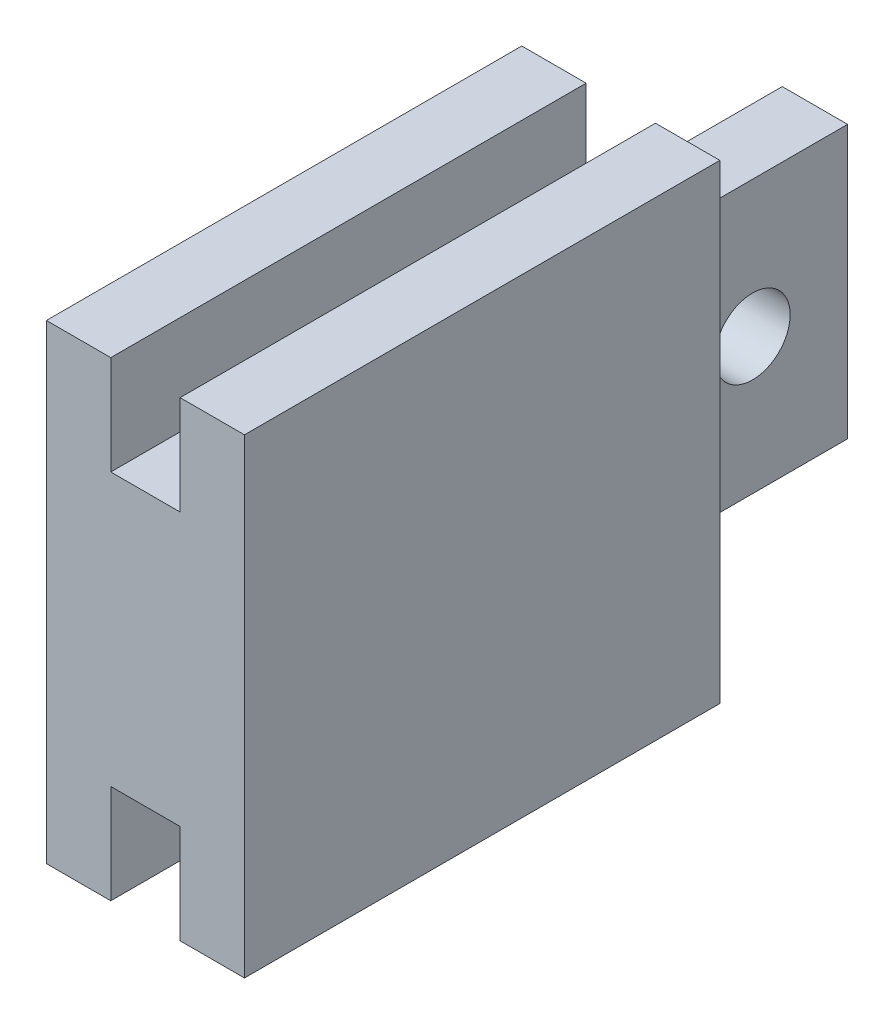
SolidWorks part; units mm, degrees
ref_plane "Front Plane" through (0, 0, 0) normal (1, 0, 0) x (0, 1, 0)
ref_plane "Top Plane" through (0, 0, 0) normal (0, 0, 1) x (0, 1, 0)
ref_plane "Right Plane" through (0, 0, 0) normal (0, 1, 0) x (-1, 0, 0)
sketch "Sketch1" plane through (0, 0, 0) normal (1, 0, 0) x (0, 1, 0)
  line L1 (0, 0) -> (23.75, 0)
  line L2 (0, 0) -> (0, 24)
  line L3 (0, 24) -> (23.75, 24)
  line L4 (23.75, 0) -> (23.75, 24)
  dimension "D1" = 23.75
  dimension "D2" = 24
extrude "Boss-Extrude1" add sketch "Sketch1" against normal blind 10
sketch "Sketch2" plane through (0, 0, 0) normal (0, -1, 0) x (1, 0, 0)
  line L1 (-10, 0) -> (-6.65, 0)
  line L2 (-10, 0) -> (-10, -9.8)
  line L3 (-10, -9.8) -> (-6.65, -9.8)
  line L4 (-6.65, 0) -> (-6.65, -9.8)
  line L5 (0, 0) -> (-3.35, 0)
  line L6 (0, 0) -> (0, -9.8)
  line L7 (0, -9.8) -> (-3.35, -9.8)
  line L8 (-3.35, 0) -> (-3.35, -9.8)
  line L9 (-6.65, -9.8) -> (-3.35, -9.8)
  line L10 (-6.65, -9.8) -> (-6.65, 0)
  line L11 (-6.65, 0) -> (-3.35, 0)
  line L12 (-3.35, -9.8) -> (-3.35, 0)
  line M12 (-10, 0) -> (0, 0)
  dimension "D1" = 9.8
  dimension "D2" = 3.35
  dimension "D3" = 3.35
extrude "Boss-Extrude2" add sketch "Sketch2" against normal through all contours L4 L9 L8 M12 region at (-5, 0, -4.9)
sketch "Sketch3" plane through (0, 0, 0) normal (0, -1, 0) x (1, 0, 0)
  line L0 (-3.35, 20.65) -> (-3.35, 3.35)
  line L1 (0, 24) -> (-10, 24)
  line L2 (0, 24) -> (0, 0)
  line L3 (0, 0) -> (-10, 0)
  line L4 (-10, 24) -> (-10, 0)
  line L5 (-3.35, 3.35) -> (-6.65, 3.35)
  line L6 (-6.65, 20.65) -> (-6.65, 3.35)
  line L7 (-3.35, 20.65) -> (-6.65, 20.65)
  line L9 (-6.65, 20.65) -> (-3.35, 20.65)
  line L10 (-6.65, 20.65) -> (-6.65, 24)
  line L11 (-6.65, 24) -> (-3.35, 24)
  line L12 (-3.35, 20.65) -> (-3.35, 24)
  dimension "D1" = 3.35
extrude "Boss-Extrude3" [suppressed] add sketch "Sketch3" along normal blind 4.9 contours L0 L7 L6 L5 | L10 L9 L12 L11
sketch "Sketch4" plane through (-6.65, 0, 0) normal (-1, 0, 0) x (0, -1, 0)
  line L0 (0, 0) -> (-23.75, 0) construction
  line L1 (-11.875, 0) -> (-23.75, 0)
  line L2 (-11.875, 0) -> (-11.875, -5)
  line L3 (-11.875, -5) -> (-23.75, -5)
  line L4 (-23.75, 0) -> (-23.75, -5)
  circle A0 centre (-11.875, -5) radius 1.9
  dimension "D2" = 3.8
extrude "Cut-Extrude1" cut sketch "Sketch4" against normal up to next contours A0
sketch "Sketch5" plane through (0, 23.75, 0) normal (0, 1, 0) x (-1, 0, 0)
  line L0 (3.25, 20.75) -> (3.25, 3.25)
  line L1 (0, 24) -> (10, 24)
  line L2 (0, 24) -> (0, 0)
  line L3 (0, 0) -> (10, 0)
  line L4 (10, 24) -> (10, 0)
  line L5 (3.25, 3.25) -> (6.75, 3.25)
  line L6 (6.75, 20.75) -> (6.75, 3.25)
  line L7 (3.25, 20.75) -> (6.75, 20.75)
  line L9 (3.25, 20.75) -> (6.75, 20.75)
  line L10 (3.25, 20.75) -> (3.25, 24)
  line L11 (3.25, 24) -> (6.75, 24)
  line L12 (6.75, 20.75) -> (6.75, 24)
  line L13 (3.25, 3.25) -> (6.75, 3.25)
  line L14 (3.25, 3.25) -> (3.25, -9.8)
  line L15 (3.25, -9.8) -> (6.75, -9.8)
  line L16 (6.75, 3.25) -> (6.75, -9.8)
  point P15 (0, 0)
  line M11 (3.35, 0) -> (3.35, -9.8)
  line M12 (3.35, -9.8) -> (6.65, -9.8)
  line M13 (6.65, -9.8) -> (6.65, 0)
  line M14 (6.65, 0) -> (10, 0)
  dimension "D1" = 3.25
extrude "Cut-Extrude2" cut sketch "Sketch5" against normal blind 5 contours L7 L12 L1 L10 | L7 L0 L5 L6 | L16 L5 L14 L3 M14 | L3 M11 M12 M13 region at (-5, 23.75, 12) region at (-5, 23.75, 22.375) region at (-5, 23.75, 1.625) region at (-5, 23.75, -4.9)
ref_plane "Plane1" through (0, 11.875, 0) normal (0, 1, 0) x (1, 0, 0)
mirror "Mirror1" about plane through (0, 11.875, 0) normal (0, 1, 0) of "Cut-Extrude2"
equation "\"whitekey_cutout_length\"= 101.5"
equation "\"key_mount_recess_length\"=50"
equation "\"key_mount_recess_height\"=12.5"
equation "\"key_mount_recess_depth\"=1.5"
equation "\"wall_thickness\"=10"
equation "\"guide_brace_height\"=20"
equation "\"guide_brace_thickness\"=2"
equation "\"dowel_recess_depth\"=10"
equation "\"dowel_recess_offset\"=3.25"
equation "\"base_mount_height\"=40"
equation "\"base_rear_length\"=80"
equation "\"base_front_length\"=111.5"
equation "\"screw_hole_wall_offset\"=7.25"
equation "\"screw_hole_edge_inset\"=\"dowel_recess_depth\"/2"
equation "\"screw_hole_diameter\"=3.8"
equation "\"screw_head_hole_diameter\"=6.7"
equation "\"screw_nut_hole_side_len\"=3.5"
equation "\"screw_shaft_diameter\"=3.5"
equation "\"switch_board_width\"=30"
equation "\"switch_board_wall_offset\"=11.5"
equation "\"heatset_insert_hole_diameter\"=4.8"
equation "\"heatset_insert_hole_depth\"=3.8"
equation "\"D1@Boss-Extrude1\"=\"wall_thickness\""
equation "\"D2@Sketch2\"=\"dowel_recess_offset\"+\"dowel_insert_tolerance\""
equation "\"D3@Sketch2\"=\"dowel_recess_offset\"+\"dowel_insert_tolerance\""
equation "\"D1@Boss-Extrude3\"=\"front_rear_panel_recess_depth\"-\"dowel_insert_tolerance\""
equation "\"D1@Sketch3\"=\"dowel_recess_offset\"+\"dowel_insert_tolerance\""
equation "\"D1@Sketch2\"=\"dowel_recess_depth\"-\"dowel_insert_tolerance\"*2"
equation "\"D1@Sketch4\"=\"screw_hole_edge_inset\""
equation "\"D2@Sketch4\"=\"screw_hole_diameter\""
equation "\"D1@Sketch5\"=\"dowel_recess_offset\""
equation "\"D1@Cut-Extrude2\"=\"front_rear_panel_recess_depth\""
equation "\"screw_nut_recess_offset\"=0.35"
equation "\"screw_head_and_nut_recess_depth\"=2.5"
equation "\"front_rear_panel_width\"=23.75"
equation "\"rod_length_adj\"=0.5"
equation "\"rod_insert_length\"=2.8"
equation "\"D1@Sketch1\"=\"front_rear_panel_width\""
equation "\"switch_board_thickness\"=1.6"
equation "\"front_panel_height\"=24"
equation "\"rod_diameter\"=5"
equation "\"rod_head_diameter\"=8"
equation "\"switch_black_key_mount_height\"=8"
equation "\"switch_white_key_mount_height\"=3"
equation "\"D2@Sketch1\"=\"front_panel_height\""
equation "\"dowel_insert_tolerance\"=0.1"
equation "\"front_rear_panel_recess_depth\"=5"
